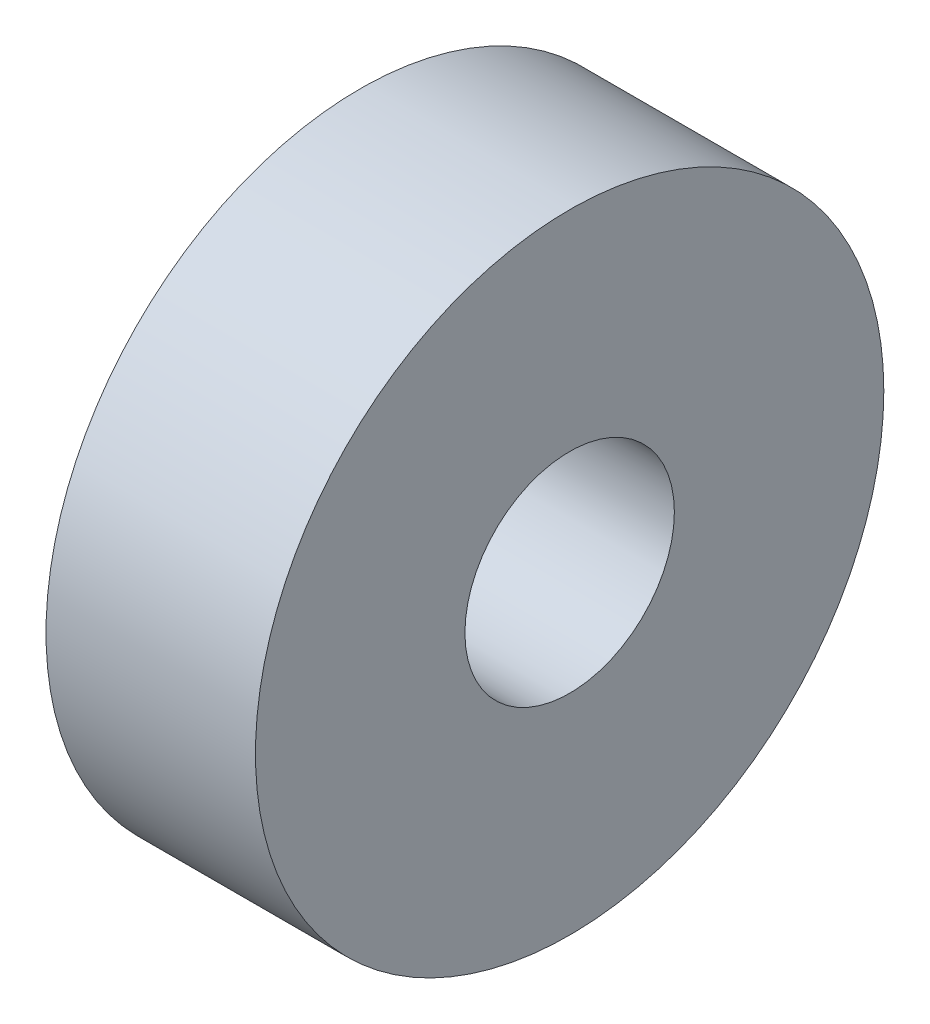
SolidWorks part; units mm, degrees
material "AISI 1045 Steel, cold drawn"
ref_plane "Front Plane" through (0, 0, 0) normal (0, 0, 1) x (1, 0, 0)
ref_plane "Top Plane" through (0, 0, 0) normal (0, 1, 0) x (1, 0, 0)
ref_plane "Right Plane" through (0, 0, 0) normal (1, 0, 0) x (0, 0, -1)
sketch "Sketch1" plane through (0, 0, 0) normal (0, 0, 1) x (1, 0, 0)
  line L0 (0, 0) -> (-13020.5493, 0) construction
  line L1 (0, 0) -> (0, 4.7625) construction
  line L2 (0, 4.7625) -> (9.525, 4.7625) construction
  line L3 (9.525, 4.7625) -> (9.525, 0) construction
  line L4 (0, 4.7625) -> (0, 14.2875)
  line L5 (0, 14.2875) -> (9.525, 14.2875)
  line L6 (9.525, 14.2875) -> (9.525, 4.7625)
  line L7 (0, 4.7625) -> (9.525, 4.7625)
  dimension "D1" = 4.7625
  dimension "D2" = 14.2875
  dimension "D3" = 9.525
revolve "Revolve1" add sketch "Sketch1" angle 360 about L0
